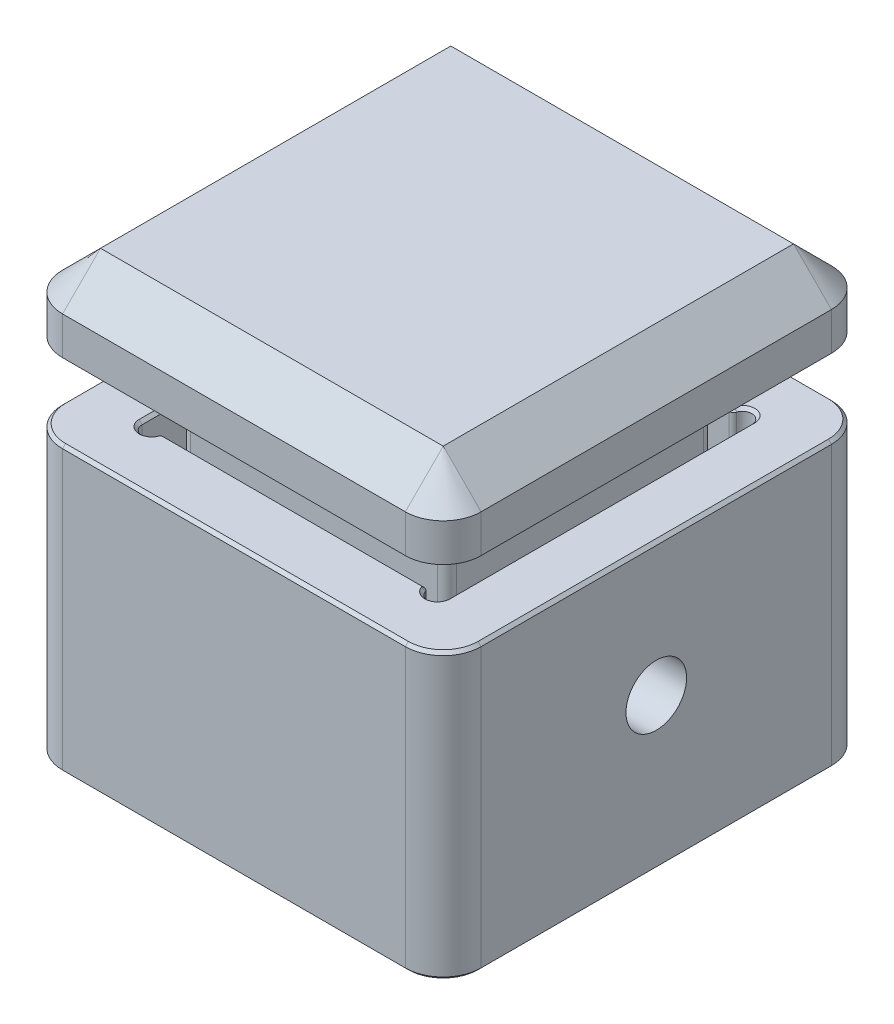
SolidWorks part; units mm, degrees
material "Nylon 101"
ref_plane "Front Plane" through (0, 0, 0) normal (0, 0, 1) x (1, 0, 0)
ref_plane "Top Plane" through (0, 0, 0) normal (0, 1, 0) x (1, 0, 0)
ref_plane "Right Plane" through (0, 0, 0) normal (1, 0, 0) x (0, 0, -1)
sketch "Sketch1" plane through (0, 0, 0) normal (0, 1, 0) x (1, 0, 0)
  line L0 (0, 12.7635) -> (25.527, 12.7635) construction
  line L1 (1.6, 0) -> (23.927, 0)
  line L2 (0, 0) -> (0, 25.527)
  line L3 (1.6, 25.527) -> (23.927, 25.527)
  line L4 (25.527, 0) -> (25.527, 25.527)
  line L5 (0, 25.527) -> (1.6, 25.527) construction
  line L6 (23.927, 25.527) -> (25.527, 25.527) construction
  line L8 (-4.7625, 30.607) -> (30.2895, 30.607)
  line L9 (-4.7625, 30.607) -> (-4.7625, -5.08)
  line L10 (-4.7625, -5.08) -> (30.2895, -5.08)
  line L11 (30.2895, 30.607) -> (30.2895, -5.08)
  arc A0 (0, 0) -> (1.6, 0) centre (0.8, 0) ccw
  arc A1 (25.527, 0) -> (23.927, 0) centre (24.727, 0) cw
  arc A2 (0, 25.527) -> (1.6, 25.527) centre (0.8, 25.527) cw
  arc A3 (25.527, 25.527) -> (23.927, 25.527) centre (24.727, 25.527) ccw
  dimension "D3" = 0.8
  dimension "D1" = 25.527
  dimension "D2" = 25.527
  dimension "D4" = 5.08
  dimension "D5" = 4.7625
  dimension "D6" = 5.08
  dimension "D7" = 4.7625
extrude "Boss-Extrude1" add sketch "Sketch1" along normal blind 23.8125
fillet "Fillet1" radius 3.175 4 edges at (-4.7625, 11.9062, -30.607) (30.2895, 11.9062, -30.607) (30.2895, 11.9062, 5.08) (-4.7625, 11.9062, 5.08)
fillet "Fillet2" radius 0.4 4 edges at (23.927, 11.9062, 0) (23.927, 11.9062, -25.527) (1.6, 11.9062, -25.527) (1.6, 11.9062, 0)
ref_plane "Plane1" through (0, 30.1625, 0) normal (0, 1, 0) x (1, 0, 0)
sketch "Sketch2" plane through (0, 30.1625, 0) normal (0, 1, 0) x (1, 0, 0)
  line L0 (25.527, 0) -> (25.527, 25.527) construction
  line L1 (0, 0) -> (25.527, 0) construction
  line L2 (0, 0) -> (0, 25.527) construction
  line L3 (0, 25.527) -> (25.527, 25.527) construction
  line L4 (27.1145, 30.607) -> (-1.5875, 30.607)
  line L5 (-4.7625, 27.432) -> (-4.7625, -1.905)
  line L6 (-1.5875, -5.08) -> (27.1145, -5.08)
  line L7 (30.2895, -1.905) -> (30.2895, 27.432)
  line L8 (27.1145, 30.607) -> (-1.5875, 30.607)
  line L9 (-4.7625, 27.432) -> (-4.7625, -1.905)
  line L10 (-1.5875, -5.08) -> (27.1145, -5.08)
  line L11 (30.2895, -1.905) -> (30.2895, 27.432)
  line L12 (25.527, 0) -> (25.527, 25.527) construction
  line L13 (23.5956, 25.527) -> (1.9314, 25.527) construction
  line L14 (1.6256, 23.9014) -> (23.9014, 23.9014)
  line L15 (23.9014, 1.6256) -> (23.9014, 23.9014)
  line L16 (1.6256, 1.6256) -> (23.9014, 1.6256)
  line L17 (1.6256, 1.6256) -> (1.6256, 23.9014)
  arc A4 (-1.5875, 30.607) -> (-4.7625, 27.432) centre (-1.5875, 27.432) ccw
  arc A5 (-4.7625, -1.905) -> (-1.5875, -5.08) centre (-1.5875, -1.905) ccw
  arc A6 (27.1145, -5.08) -> (30.2895, -1.905) centre (27.1145, -1.905) ccw
  arc A7 (30.2895, 27.432) -> (27.1145, 30.607) centre (27.1145, 27.432) ccw
  arc A8 (-1.5875, 30.607) -> (-4.7625, 27.432) centre (-1.5875, 27.432) ccw
  arc A9 (-4.7625, -1.905) -> (-1.5875, -5.08) centre (-1.5875, -1.905) ccw
  arc A10 (27.1145, -5.08) -> (30.2895, -1.905) centre (27.1145, -1.905) ccw
  arc A11 (30.2895, 27.432) -> (27.1145, 30.607) centre (27.1145, 27.432) ccw
  dimension "D1" = 0
  dimension "D2" = 1.6256
extrude "Boss-Extrude2" add sketch "Sketch2" along normal blind 6.35 separate body contours L17 L16 L15 L14 | L11 A11 L8 A8 L9 A9 L10 A10 L16 L17 L14 L15 region at (29.0059, 30.1625, -29.3234) region at (12.7635, 30.1625, -12.7635)
extrude "Boss-Extrude3" add sketch "Sketch2<4>" against normal up to surface (30.1625 mm away) contours L17 L16 L15 L14 region at (12.7635, 30.1625, -12.7635) up to face at (12.7635, 0, -12.7635)
sketch "Sketch2<4>" plane through (0, 30.1625, 0) normal (0, 1, 0) x (1, 0, 0) same geometry as "Sketch2"
chamfer "Chamfer1" distance 3.175 angle 45 8 edges at (29.3596, 36.5125, 4.1501) (12.7635, 36.5125, 5.08) (-3.8326, 36.5125, 4.1501) (-4.7625, 36.5125, -12.7635) (-3.8326, 36.5125, -29.6771) (12.7635, 36.5125, -30.607) (29.3596, 36.5125, -29.6771) (30.2895, 36.5125, -12.7635)
chamfer "Chamfer2" distance 4.7625 angle 45 4 edges at (1.6256, 0, -12.7635) (12.7635, 0, -1.6256) (23.9014, 0, -12.7635) (12.7635, 0, -23.9014)
chamfer "Chamfer3" distance 0.254 angle 45 40 edges at (25.527, 23.8125, -12.7635) (24.8623, 23.8125, -26.3155) (23.8266, 23.8125, -25.6004) (12.7635, 23.8125, -25.527) (1.7004, 23.8125, -25.6004) (0.6647, 23.8125, -26.3155) (0, 23.8125, -12.7635) (0.6647, 23.8125, 0.7885) (1.7004, 23.8125, 0.0734) (12.7635, 23.8125, 0) (23.8266, 23.8125, 0.0734) (24.8623, 23.8125, 0.7885) (29.3596, 23.8125, -29.6771) (30.2895, 23.8125, -12.7635) (29.3596, 23.8125, 4.1501) (12.7635, 23.8125, 5.08) (-3.8326, 23.8125, 4.1501) (-4.7625, 23.8125, -12.7635) (-3.8326, 23.8125, -29.6771) (12.7635, 23.8125, -30.607) (1.7004, 0, 0.0734) (0.6647, 0, 0.7885) (0, 0, -12.7635) (0.6647, 0, -26.3155) (1.7004, 0, -25.6004) (12.7635, 0, -25.527) (23.8266, 0, -25.6004) (24.8623, 0, -26.3155) (25.527, 0, -12.7635) (24.8623, 0, 0.7885) (23.8266, 0, 0.0734) (12.7635, 0, 0) (-3.8326, 0, 4.1501) (12.7635, 0, 5.08) (29.3596, 0, 4.1501) (30.2895, 0, -12.7635) (29.3596, 0, -29.6771) (12.7635, 0, -30.607) (-3.8326, 0, -29.6771) (-4.7625, 0, -12.7635)
fillet "Fillet3" radius 0.8106 4 edges at (1.6256, 17.4625, -23.9014) (23.9014, 17.4625, -1.6256) (1.6256, 17.4625, -1.6256) (23.9014, 17.4625, -23.9014)
sketch "Sketch3" plane through (30.2895, 0, 0) normal (1, 0, 0) x (0, 0, -1)
  line L2 (27.432, 23.5585) -> (-1.905, 23.5585) construction
  line L3 (12.7635, 0.254) -> (12.7635, 23.5585) construction
  line L4 (-1.905, 0.254) -> (27.432, 0.254) construction
  line L5 (-1.905, 30.1625) -> (27.432, 30.1625) construction
  circle A0 centre (12.7635, 12.7) radius 2.54
  dimension "D3" = 5.08
  dimension "D1" = 17.4625
extrude "Cut-Extrude1" cut sketch "Sketch3" against normal through all
equation "\"D3@Sketch1\"=0.4mm *2"
